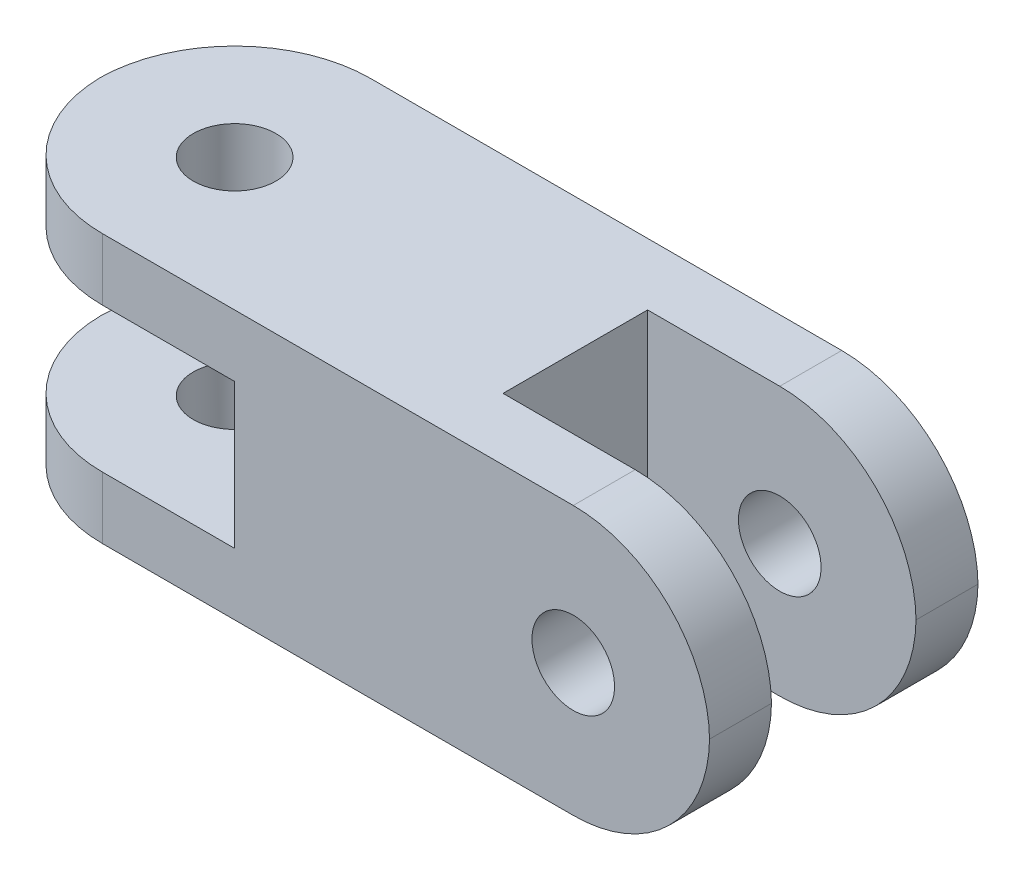
SolidWorks part; units mm, degrees
ref_plane "Plano frontal" through (0, 0, 0) normal (0, 0, 1) x (1, 0, 0)
ref_plane "Plano superior" through (0, 0, 0) normal (0, 1, 0) x (1, 0, 0)
ref_plane "Plano direito" through (0, 0, 0) normal (1, 0, 0) x (0, 0, -1)
sketch "Esboço1" plane through (0, 0, 0) normal (0, 0, 1) x (1, 0, 0)
  line L1 (-90, 32.5) -> (90, 32.5)
  line L2 (-90, 32.5) -> (-90, -32.5)
  line L3 (-90, -32.5) -> (90, -32.5)
  line L4 (90, 32.5) -> (90, -32.5)
  line L5 (-90, 32.5) -> (90, -32.5) construction
  line L6 (-90, -32.5) -> (90, 32.5) construction
  point P0 (0, 0)
  dimension "D1" = 180
  dimension "D2" = 65
extrude "Ressalto-extrusão2" add sketch "Esboço1" along normal mid plane 65
fillet "Filete1" radius 33 2 edges at (-90, 0, 32.5) (-90, 0, -32.5)
sketch "Esboço2" plane through (0, 0, 0) normal (0, 0, 1) x (1, 0, 0)
  line L0 (-89.9962, 32.5) -> (-89.9962, -32.5) construction
  line L1 (-89.9962, 17.5) -> (-24.9962, 17.5)
  line L2 (-89.9962, 17.5) -> (-89.9962, -17.5)
  line L3 (-89.9962, -17.5) -> (-24.9962, -17.5)
  line L4 (-24.9962, 17.5) -> (-24.9962, -17.5)
  line L5 (-57, 32.5) -> (-89.9962, 32.5) construction
  line L6 (-89.9962, -32.5) -> (-57, -32.5) construction
  dimension "D1" = 15
  dimension "D2" = 15
  dimension "D3" = 65
sketch "Esboço3" plane through (0, 0, 0) normal (0, 0, 1) x (1, 0, 0)
extrude "Corte-extrusão1" cut sketch "Esboço2" against normal through all both and the other way through all
fillet "Filete4" radius 33 2 edges at (90, -32.5, 0) (90, 32.5, 0)
sketch "Esboço4" plane through (0, 32.5, 0) normal (0, 1, 0) x (1, 0, 0)
  line L0 (89.9962, 32.5) -> (89.9962, -32.5) construction
  line L1 (89.9962, 17.5) -> (24.9962, 17.5)
  line L2 (89.9962, 17.5) -> (89.9962, -17.5)
  line L3 (89.9962, -17.5) -> (24.9962, -17.5)
  line L4 (24.9962, 17.5) -> (24.9962, -17.5)
  line L5 (89.9962, 32.5) -> (57, 32.5) construction
  line L6 (57, -32.5) -> (89.9962, -32.5) construction
  dimension "D1" = 15
  dimension "D2" = 15
  dimension "D3" = 65
extrude "Corte-extrusão2" cut sketch "Esboço4" against normal through all
sketch "Esboço5" plane through (0, 0, -32.5) normal (0, 0, -1) x (-1, 0, 0)
  circle A0 centre (-57, -0.5) radius 10
  dimension "D1" = 20
extrude "Corte-extrusão3" cut sketch "Esboço5" against normal through all
sketch "Esboço6" plane through (0, 32.5, 0) normal (0, 1, 0) x (1, 0, 0)
  circle A0 centre (-57, -0.5) radius 10
  dimension "D1" = 20
extrude "Corte-extrusão4" cut sketch "Esboço6" against normal through all
